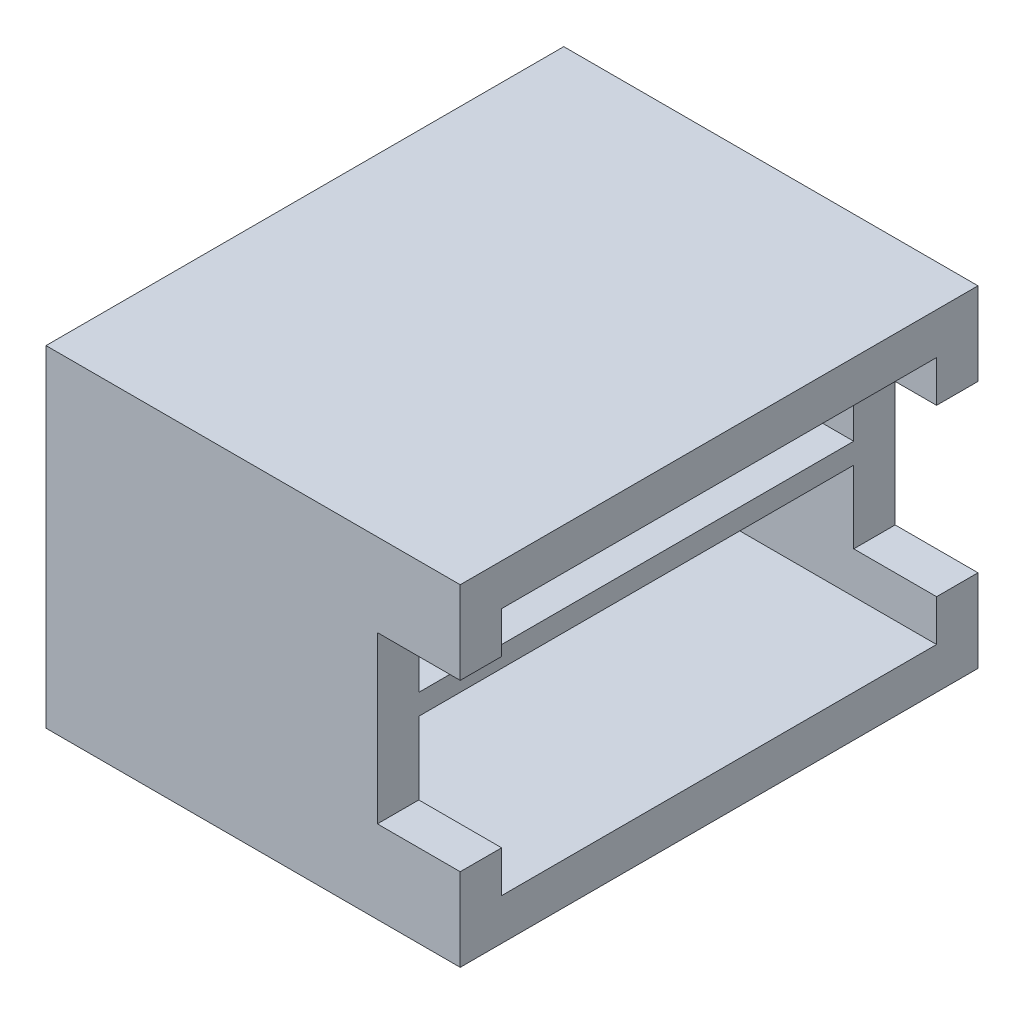
SolidWorks part; units mm, degrees
ref_plane "Front Plane" through (0, 0, 0) normal (0, 0, 1) x (1, 0, 0)
ref_plane "Top Plane" through (0, 0, 0) normal (0, 1, 0) x (1, 0, 0)
ref_plane "Right Plane" through (0, 0, 0) normal (1, 0, 0) x (0, 0, -1)
sketch "Croquis1" plane through (0, 0, 0) normal (0, 1, 0) x (1, 0, 0)
  line L1 (-10, 12.5) -> (10, 12.5)
  line L2 (-10, 12.5) -> (-10, -12.5)
  line L3 (-10, -12.5) -> (10, -12.5)
  line L4 (10, 12.5) -> (10, -12.5)
  line L5 (-10, 12.5) -> (10, -12.5) construction
  line L6 (-10, -12.5) -> (10, 12.5) construction
  point P0 (0, 0)
  dimension "D1" = 20
  dimension "D2" = 25
extrude "Saliente-Extruir4" add sketch "Croquis1" along normal blind 16
sketch "Croquis4" plane through (0, 0, 0) normal (1, 0, 0) x (0, 0, -1)
  line L0 (-12.5, 16) -> (12.5, 16) construction
  line L1 (-10.5, 14) -> (10.5, 14)
  line L2 (-10.5, 14) -> (-10.5, 2)
  line L3 (-10.5, 2) -> (10.5, 2)
  line L4 (10.5, 14) -> (10.5, 2)
  line L5 (-10.5, 14) -> (10.5, 2) construction
  line L6 (-10.5, 2) -> (10.5, 14) construction
  line L7 (-12.5, 16) -> (-12.5, 0) construction
  line L8 (-12.5, 0) -> (12.5, 0) construction
  line L9 (12.5, 16) -> (12.5, 0) construction
  point P0 (0, 8)
  dimension "D1" = 2
  dimension "D2" = 2
  dimension "D3" = 2
  dimension "D4" = 2
extrude "Cortar-Extruir1" cut sketch "Croquis4" against normal blind 18 from surface starting at face at (10, 8, 0)
sketch "Croquis5" plane through (0, 0, 0) normal (1, 0, 0) x (0, 0, -1)
  line L0 (10.5, 14) -> (-10.5, 14) construction
  line L2 (10.5, 2) -> (10.5, 14) construction
  line L3 (-10.5, 8.5) -> (10.5, 8.5)
  line L4 (-10.5, 8.5) -> (-10.5, 7.5)
  line L5 (-10.5, 7.5) -> (10.5, 7.5)
  line L6 (10.5, 8.5) -> (10.5, 7.5)
  line L7 (-10.5, 8.5) -> (10.5, 7.5) construction
  line L8 (-10.5, 7.5) -> (10.5, 8.5) construction
  point P4 (0, 8)
  dimension "D1" = 1
  dimension "D2" = 21
  dimension "D3" = 0
  dimension "D4" = 5.5
extrude "Saliente-Extruir6" add sketch "Croquis5" along normal blind 16 from surface starting at face at (-10, 8, 0)
sketch "Croquis7" plane through (0, 0, 0) normal (1, 0, 0) x (0, 0, -1)
  line L0 (-12.5, 16) -> (-12.5, 0) construction
  line L1 (-12.5, 12) -> (-10.5, 12)
  line L2 (-12.5, 12) -> (-12.5, 4)
  line L3 (-12.5, 4) -> (-10.5, 4)
  line L4 (-10.5, 12) -> (-10.5, 4)
  line L5 (-12.5, 12) -> (-10.5, 4) construction
  line L6 (-12.5, 4) -> (-10.5, 12) construction
  line L7 (-10.5, 7.5) -> (-10.5, 2) construction
  line L9 (-12.5, 16) -> (12.5, 16) construction
  line L10 (-12.5, 0) -> (12.5, 0) construction
  line L11 (0, 8) -> (0, 5.1009) construction
  line L12 (12.5, 12) -> (12.5, 4)
  line L13 (12.5, 4) -> (10.5, 4)
  line L14 (10.5, 12) -> (10.5, 4)
  line L15 (12.5, 4) -> (10.5, 12) construction
  line L16 (12.5, 12) -> (10.5, 4) construction
  line L17 (12.5, 12) -> (10.5, 12)
  point P0 (-11.5, 8)
  dimension "D1" = 0
  dimension "D2" = 0
  dimension "D3" = 4
  dimension "D4" = 4
extrude "Saliente-Extruir7" add sketch "Croquis7" along normal blind 4 from surface starting at face at (10, 8, 0)
extrude "Cortar-Extruir2" cut sketch "Croquis7<2>" against normal blind 8 from surface starting at face at (14, 8, 11.5)
sketch "Croquis7<2>" plane through (0, 0, 0) normal (1, 0, 0) x (0, 0, -1) same geometry as "Croquis7"
sketch "Croquis8" plane through (0, 0, 0) normal (0, 1, 0) x (1, 0, 0)
  line L0 (10, 12.5) -> (-10, 12.5) construction
  line L1 (-10, 5.5) -> (2.75, 5.5)
  line L2 (-10, 5.5) -> (-10, -5.5)
  line L3 (-10, -5.5) -> (2.75, -5.5)
  line L4 (2.75, 5.5) -> (2.75, -5.5)
  line L5 (-10, 5.5) -> (2.75, -5.5) construction
  line L6 (-10, -5.5) -> (2.75, 5.5) construction
  line L7 (-10, 12.5) -> (-10, -12.5) construction
  point P0 (-3.625, 0)
  point P5 (-4, 0)
  point P6 (-4, 0)
  dimension "D1" = 12.75
  dimension "D2" = 0
  dimension "D3" = 11
  dimension "D4" = 7
extrude "Saliente-Extruir8" add sketch "Croquis8" against normal blind 3
sketch "Croquis9" plane through (0, 0, 0) normal (0, 0, 1) x (1, 0, 0)
  line L0 (-10, 0) -> (10, 0) construction
  line L1 (-8.5, 0) -> (1.25, 0)
  line L2 (-8.5, 0) -> (-8.5, -1.5)
  line L3 (-8.5, -1.5) -> (1.25, -1.5)
  line L4 (1.25, 0) -> (1.25, -1.5)
  line L5 (-8.5, 0) -> (1.25, -1.5) construction
  line L6 (-8.5, -1.5) -> (1.25, 0) construction
  line L7 (-10, -3) -> (2.75, -3) construction
  line L8 (-10, -3) -> (-10, 0) construction
  line L9 (2.75, -3) -> (2.75, 0) construction
  point P0 (-3.625, -0.75)
  dimension "D1" = 0
  dimension "D2" = 1.5
  dimension "D3" = 1.5
  dimension "D4" = 1.5
extrude "Cortar-Extruir4" cut sketch "Croquis9" against normal mid plane 43
